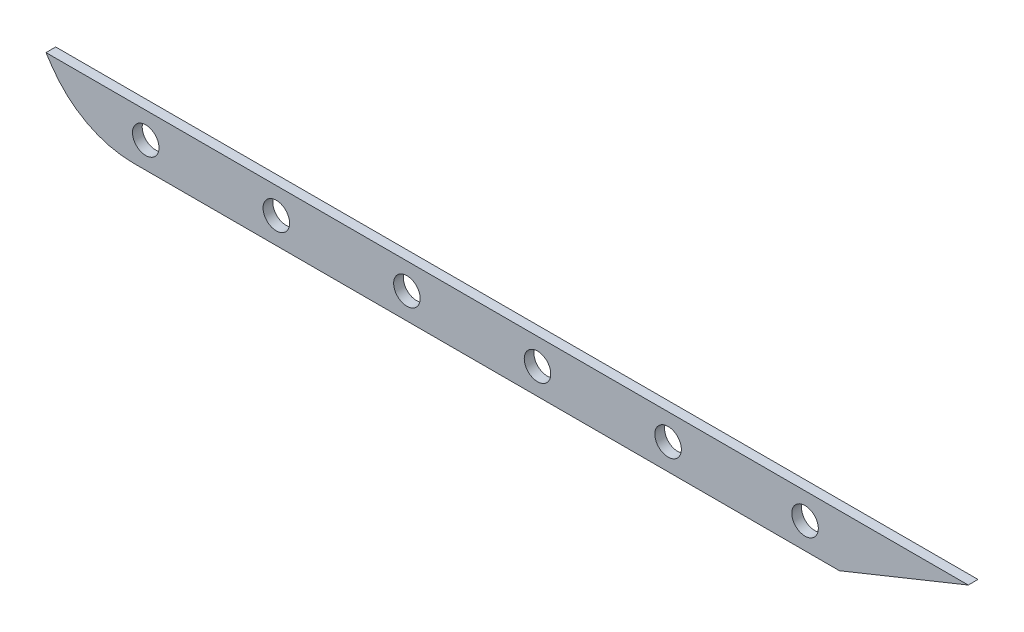
SolidWorks part; units mm, degrees
material "5052-H32"
ref_plane "Front Plane" through (0, 0, 0) normal (0, 0, 1) x (1, 0, 0)
ref_plane "Top Plane" through (0, 0, 0) normal (0, 1, 0) x (1, 0, 0)
ref_plane "Right Plane" through (0, 0, 0) normal (1, 0, 0) x (0, 0, -1)
sketch "Sketch1" plane through (0, 0, 0) normal (0, 0, 1) x (1, 0, 0)
  line L1 (428.1206, 33.3333) -> (428.1206, 28.5708)
  line L3 (428.1206, 28.5708) -> (0, 28.5708)
  line L4 (0, 28.5708) -> (-98.8794, 3.851)
  line L6 (-98.8794, 3.851) -> (-31.8794, -96.649)
  line L7 (428.1206, 28.5708) -> (403.1206, -71.149)
  line L9 (403.1206, -71.149) -> (366, -96.649)
  line L10 (-31.8794, -96.649) -> (366, -96.649)
  circle A0 centre (0, -83.899) radius 6.5
  circle A1 centre (64, -83.899) radius 6.5
  circle A2 centre (128, -83.899) radius 6.5
  circle A3 centre (192, -83.899) radius 6.5
  circle A4 centre (256, -83.899) radius 6.5
  circle A5 centre (323.1206, -83.899) radius 6.5
  point P0 (-48.8794, -71.149)
  point P2 (-31.8794, -96.649)
  point P8 (48, -83.899)
  point P9 (403.1206, -71.149)
  dimension "D2" = 48
  dimension "D4" = 64
  dimension "D1" = 25.5
  dimension "D3" = 75
  dimension "D5" = 25
  dimension "D6" = 80
  dimension "D7" = 527
  dimension "D9" = 64
  dimension "D10" = 64
  dimension "D11" = 64
  dimension "D12" = 123.69
  dimension "D13" = 12.75
extrude "Boss-Extrude1" add sketch "Sketch1" along normal blind 4.7625 contours L3 L4 L6 L10 L9 L7
extrude "Cut-Extrude1" cut sketch "Sketch1<4>" along normal through all contours A0 | A1 | A2 | A3 | A4 | A5 region at (0, -83.899, 0)
sketch "Sketch1<4>" plane through (0, 0, 0) normal (0, 0, 1) x (1, 0, 0) same geometry as "Sketch1"
sketch "Sketch2" plane through (0, 0, 0) normal (0, 0, -1) x (-1, 0, 0)
  circle A0 centre (-291.1206, -83.899) radius 6.5
  circle A2 centre (-241.5603, -124.3932) radius 6.5
  circle A3 centre (-192, -83.899) radius 6.5
  circle A4 centre (-128, -83.899) radius 6.5
  circle A5 centre (-64, -83.899) radius 6.5
  circle A6 centre (0, -83.899) radius 6.5
  dimension "D2" = 0
  dimension "D3" = 64
  dimension "D4" = 64
  dimension "D5" = 64
  dimension "D6" = 64
  dimension "D7" = 64
  dimension "D1" = 32
sketch "Sketch5" plane through (0, 0, 0) normal (0, 0, -1) x (-1, 0, 0)
  line L0 (48.8794, -71.149) -> (-14.2353, -96.649)
  line L1 (31.8794, -96.649) -> (-366, -96.649) construction
  line L2 (-14.2353, -96.649) -> (31.8794, -96.649)
  line L3 (31.8794, -96.649) -> (48.8794, -71.149)
  line L6 (-366, -96.649) -> (-403.1206, -71.149)
  line L7 (-403.1206, -71.149) -> (-352, -71.149)
  line L9 (-352, -71.149) -> (-326.5, -96.649)
  line L11 (-366, -96.649) -> (-326.5, -96.649)
  dimension "D1" = 22
  dimension "D2" = 45
extrude "Cut-Extrude2" [suppressed] cut sketch "Sketch5" against normal up to next
sketch "Sketch6" plane through (0, 0, 4.7625) normal (0, 0, 1) x (1, 0, 0)
  line L0 (-48.8794, -71.149) -> (14.2353, -96.649)
  line L1 (-31.8794, -96.649) -> (366, -96.649) construction
  line L2 (14.2353, -96.649) -> (-31.8794, -96.649)
  line L3 (-31.8794, -96.649) -> (-48.8794, -71.149)
  dimension "D1" = 158
sketch "Sketch7" plane through (0, 0, 4.7625) normal (0, 0, 1) x (1, 0, 0)
  line L0 (-48.8794, -71.149) -> (403.1206, -71.149)
  line L1 (-48.8794, -71.149) -> (-98.8794, 3.851)
  line L2 (-98.8794, 3.851) -> (0, 28.5708)
  line L3 (0, 28.5708) -> (428.1206, 28.5708)
  line L4 (428.1206, 28.5708) -> (403.1206, -71.149)
extrude "Cut-Extrude4" cut sketch "Sketch7" against normal up to next
fillet "Fillet1" radius 48 1 edges at (-31.8794, -96.649, 2.3813)
sketch "Sketch8" plane through (0, 0, 4.7625) normal (0, 0, 1) x (1, 0, 0)
  line L0 (403.1206, -71.149) -> (340.0059, -96.649)
  line L1 (-31.8794, -96.649) -> (366, -96.649) construction
  line L2 (340.0059, -96.649) -> (366, -96.649)
  line L3 (366, -96.649) -> (403.1206, -71.149)
  dimension "D1" = 22
extrude "Cut-Extrude5" cut sketch "Sketch8" against normal blind 10
